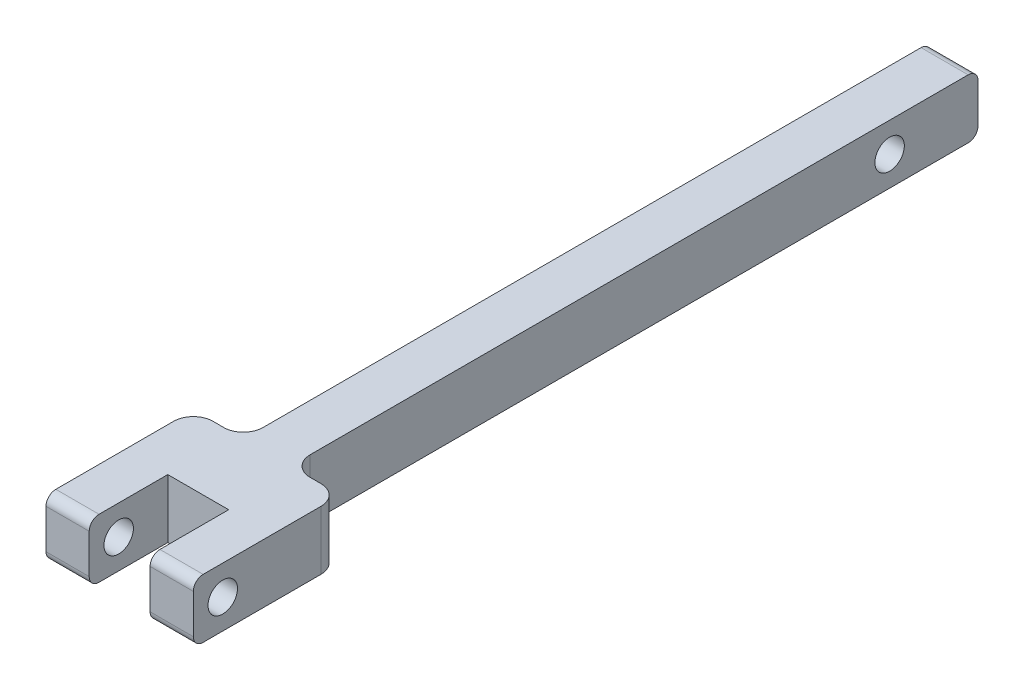
SolidWorks part; units mm, degrees
ref_plane "Alzado" through (0, 0, 0) normal (0, 0, 1) x (1, 0, 0)
ref_plane "Planta" through (0, 0, 0) normal (0, 1, 0) x (1, 0, 0)
ref_plane "Vista lateral" through (0, 0, 0) normal (1, 0, 0) x (0, 0, -1)
sketch "Croquis1" plane through (0, 0, 0) normal (1, 0, 0) x (0, 0, -1)
  line L0 (-41.5, 3) -> (41.5, 3)
  line L2 (-42.5, 0) -> (42.5, 0) construction
  line L3 (-42.5, 2) -> (-42.5, -2)
  line L4 (-41.5, -3) -> (41.5, -3)
  line L5 (42.5, 2) -> (42.5, -2)
  arc A0 (-42.5, -2) -> (-41.5, -3) centre (-41.5, -2) ccw
  arc A1 (-42.5, 2) -> (-41.5, 3) centre (-41.5, 2) cw
  arc A2 (41.5, -3) -> (42.5, -2) centre (41.5, -2) ccw
  arc A3 (41.5, 3) -> (42.5, 2) centre (41.5, 2) cw
  point P1 (0, 0)
  point P9 (-42.5, -3)
  point P13 (-42.5, 3)
  point P16 (42.5, -3)
  point P19 (42.5, 3)
  dimension "D3" = 1
  dimension "D4" = 1
  dimension "D1" = 3
  dimension "D2" = 85
extrude "Saliente-Extruir1" add sketch "Croquis1" along normal mid plane 4.8
sketch "Croquis2" plane through (0, 0, 0) normal (1, 0, 0) x (0, 0, -1)
  line L0 (-42.5, 2) -> (-42.5, -2) construction
  line L1 (42.5, -2) -> (42.5, 2) construction
  circle A0 centre (-39.5, 0) radius 1.5
  circle A1 centre (33.5, 0) radius 1.5
  dimension "D1" = 3
  dimension "D3" = 3
  dimension "D2" = 3
  dimension "D4" = 9
extrude "Cortar-Extruir1" cut sketch "Croquis2" against normal through all both and the other way through all
sketch "Croquis3" plane through (0, 0, 0) normal (1, 0, 0) x (0, 0, -1)
  line L0 (-42.5, 2) -> (-42.5, -2) construction
  line L1 (-42.5, 2) -> (-42.5, -2)
  line L2 (-41.5, 3) -> (-27.5, 3)
  line L3 (41.5, 3) -> (-41.5, 3) construction
  line L4 (-27.5, 3) -> (-27.5, -3)
  line L5 (-41.5, -3) -> (41.5, -3) construction
  line L6 (-27.5, -3) -> (-41.5, -3)
  circle A0 centre (-39.5, 0) radius 1.5 construction
  circle A1 centre (-39.5, 0) radius 1.5
  arc A2 (-41.5, 3) -> (-42.5, 2) centre (-41.5, 2) ccw construction
  arc A3 (-41.5, 3) -> (-42.5, 2) centre (-41.5, 2) ccw
  arc A4 (-42.5, -2) -> (-41.5, -3) centre (-41.5, -2) ccw construction
  arc A5 (-42.5, -2) -> (-41.5, -3) centre (-41.5, -2) ccw
  dimension "D1" = 15
extrude "Saliente-Extruir2" add sketch "Croquis3" along normal mid plane 15
sketch "Croquis4" plane through (0, 0, 0) normal (1, 0, 0) x (0, 0, -1)
  line L0 (-41.5, 3) -> (-34.5, 3)
  line L1 (-27.5, 3) -> (-41.5, 3) construction
  line L2 (-34.5, 3) -> (-34.5, -3)
  line L3 (-41.5, -3) -> (-27.5, -3) construction
  line L4 (-42.5, 2) -> (-42.5, -2)
  line L5 (-41.5, -3) -> (-27.5, -3)
  line L6 (-27.5, -3) -> (-27.5, 3)
  line L7 (-27.5, 3) -> (-41.5, 3)
  line L8 (-42.5, 2) -> (-42.5, -2)
  line L12 (-34.5, -3) -> (-41.5, -3)
  arc A2 (-41.5, 3) -> (-42.5, 2) centre (-41.5, 2) ccw
  arc A3 (-42.5, -2) -> (-41.5, -3) centre (-41.5, -2) ccw
  arc A4 (-41.5, 3) -> (-42.5, 2) centre (-41.5, 2) ccw
  arc A5 (-42.5, -2) -> (-41.5, -3) centre (-41.5, -2) ccw
  dimension "D2" = 8
  dimension "D1" = 0
extrude "Cortar-Extruir2" cut sketch "Croquis4" against normal mid plane 6.2
fillet "Redondeo1" radius 2 4 edges at (2.4, 0, 27.5) (-2.4, 0, 27.5) (7.5, 0, 27.5) (-7.5, 0, 27.5)
